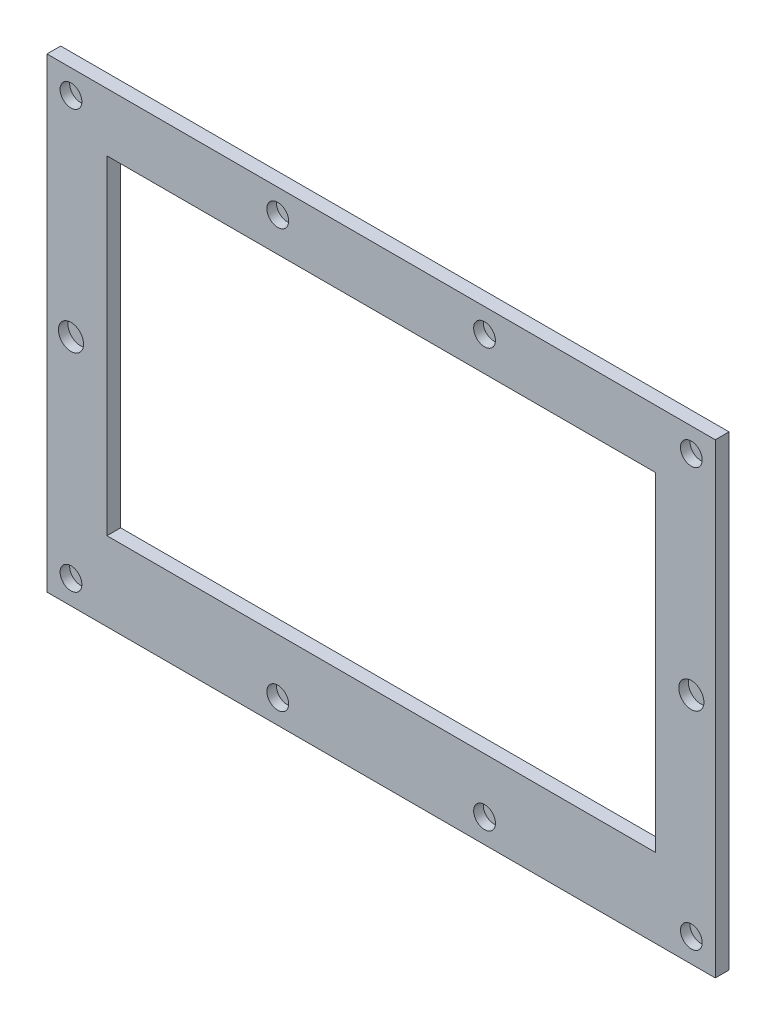
SolidWorks part; units mm, degrees
ref_plane "Front Plane" through (0, 0, 0) normal (0, 0, 1) x (1, 0, 0)
ref_plane "Top Plane" through (0, 0, 0) normal (0, 1, 0) x (1, 0, 0)
ref_plane "Right Plane" through (0, 0, 0) normal (1, 0, 0) x (0, 0, -1)
sketch "Sketch1" plane through (0, 0, 0) normal (0, 0, 1) x (1, 0, 0)
  line L1 (85.5, -56) -> (-85.5, -56)
  line L2 (85.5, -56) -> (85.5, 56)
  line L3 (85.5, 56) -> (-85.5, 56)
  line L4 (-85.5, -56) -> (-85.5, 56)
  line L5 (85.5, -56) -> (-85.5, 56) construction
  line L6 (85.5, 56) -> (-85.5, -56) construction
  line L11 (80, -45) -> (-80, -45)
  line L12 (80, -45) -> (80, 51)
  line L13 (80, 51) -> (-80, 51)
  line L14 (-80, -45) -> (-80, 51)
  line L15 (80, -45) -> (-80, 51) construction
  line L16 (80, 51) -> (-80, -45) construction
  line L17 (-14.5, -56) -> (14.5, -56)
  line L18 (-14.5, -56) -> (-14.5, -59)
  line L19 (-14.5, -59) -> (14.5, -59)
  line L20 (14.5, -56) -> (14.5, -59)
  line L21 (97.5, 68) -> (-97.5, 68)
  line L22 (97.5, 68) -> (97.5, -68)
  line L23 (97.5, -68) -> (-97.5, -68)
  line L24 (-97.5, 68) -> (-97.5, -68)
  line L25 (97.5, 68) -> (-97.5, -68) construction
  line L26 (97.5, -68) -> (-97.5, 68) construction
  point P0 (0, 0)
  point P6 (0, 0)
  point P7 (0, 3)
  point P16 (0, 0)
  dimension "D1" = 171
  dimension "D2" = 112
  dimension "D3" = 96
  dimension "D4" = 160
  dimension "D5" = 5
  dimension "D6" = 71
  dimension "D7" = 29
  dimension "D8" = 3
  dimension "D9" = 12
  dimension "D10" = 17.5
  dimension "D11" = 12
extrude "Boss-Extrude1" add sketch "Sketch1" against normal blind 2 contours L4 L1 L2 L3 L11 L14 L13 L12 | L21 L24 L23 L22 L1 L20 L19 L18 L4 L3 L2 | L20 L1 L18 L19 region at (50, -53.9559, 0) region at (0, -57.5, 0) region at (95.1226, 0, 0)
extrude "Boss-Extrude2" add sketch "Sketch1<3>" along normal blind 2 contours L21 L24 L23 L22 L1 L20 L19 L18 L4 L3 L2 | L4 L1 L2 L3 L11 L14 L13 L12 | L20 L1 L18 L19 region at (50, -53.9559, 0) region at (0, -57.5, 0) region at (95.1226, 0, 0)
sketch "Sketch1<3>" plane through (0, 0, 0) normal (0, 0, 1) x (1, 0, 0) same geometry as "Sketch1"
sketch "Sketch2" plane through (0, 0, 2) normal (0, 0, 1) x (1, 0, 0)
  line L0 (97.5, 68) -> (-97.5, 68) construction
  line L1 (90.5, -61) -> (-90.5, -61) construction
  line L2 (90.5, -61) -> (90.5, 61) construction
  line L3 (90.5, 61) -> (-90.5, 61) construction
  line L4 (-90.5, -61) -> (-90.5, 61) construction
  line L5 (90.5, -61) -> (-90.5, 61) construction
  line L6 (90.5, 61) -> (-90.5, -61) construction
  line L7 (-97.5, 68) -> (-97.5, -68) construction
  line L8 (-90.5, 61) -> (-30.1667, 61) construction
  line L9 (-30.1667, 61) -> (30.1667, 61) construction
  line L10 (30.1667, 61) -> (90.5, 61) construction
  line L11 (-90.5, 61) -> (-30.1667, 61) construction
  line L12 (-30.1667, 61) -> (30.1667, 61) construction
  line L13 (30.1667, 61) -> (90.5, 61) construction
  line L14 (90.5, 61) -> (90.5, 0) construction
  line L15 (90.5, 0) -> (90.5, -61) construction
  circle A0 centre (-90.5, 61) radius 3.175
  circle A2 centre (90.5, 61) radius 3.175
  circle A3 centre (90.5, -61) radius 3.175
  circle A5 centre (-90.5, -61) radius 3.175
  circle A6 centre (-30.1667, -61) radius 3.175
  circle A7 centre (30.1667, -61) radius 3.175
  circle A8 centre (90.5, 0) radius 3.6737
  circle A9 centre (-30.1667, 61) radius 3.175
  circle A10 centre (30.1667, 61) radius 3.175
  circle A11 centre (-90.5, 0) radius 3.6737
  point P0 (0, 0)
  point P26 (0, 0)
  dimension "D1" = 6.35
  dimension "D2" = 7
  dimension "D3" = 7
extrude "Cut-Extrude1" cut sketch "Sketch2" against normal blind 2.794
